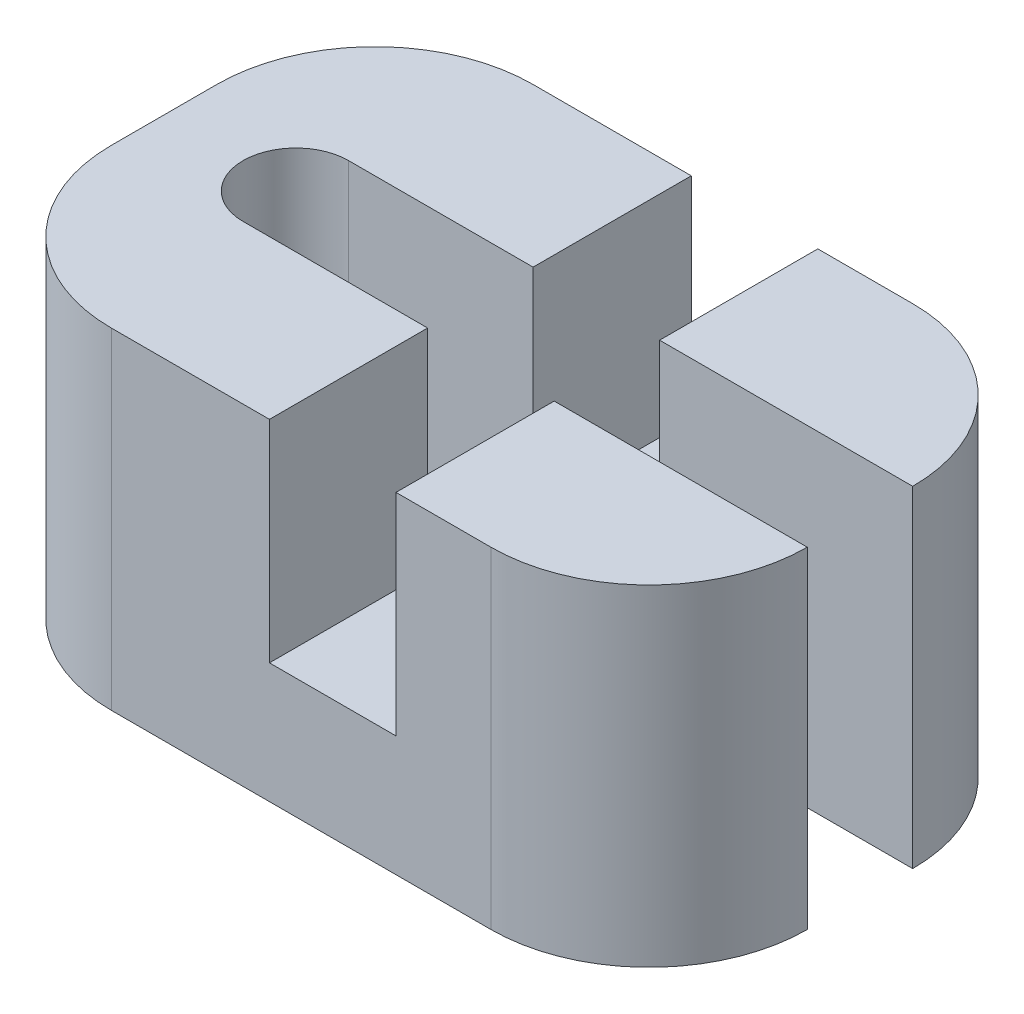
SolidWorks part; units mm, degrees
ref_plane "Alzado" through (0, 0, 0) normal (0, 0, 1) x (1, 0, 0)
ref_plane "Planta" through (0, 0, 0) normal (0, 1, 0) x (1, 0, 0)
ref_plane "Vista lateral" through (0, 0, 0) normal (1, 0, 0) x (0, 0, -1)
sketch "Croquis1" plane through (0, 0, 0) normal (0, 1, 0) x (1, 0, 0)
  line L0 (126.4716, 0) -> (0, 0) construction
  line L1 (15, 10) -> (-18, 10)
  line L2 (15, 10) -> (15, -10)
  line L3 (15, -10) -> (-18, -10)
  line L4 (-18, 10) -> (-18, -10)
  line L5 (0, 0) -> (0, 99.3902) construction
  dimension "D1" = 15
  dimension "D2" = 18
  dimension "D3" = 10
  dimension "D4" = 10
extrude "Saliente-Extruir1" add sketch "Croquis1" along normal blind 15.7
sketch "Croquis2" plane through (0, 15.7, 0) normal (0, 1, 0) x (1, 0, 0)
  line L0 (0, -13.5785) -> (0, 11.5662) construction
  line L1 (17.9678, 0) -> (-18.423, 0) construction
  circle A0 centre (-11.75, 0) radius 2.5
  circle A1 centre (11.75, 0) radius 2.5
  point P5 (-11.75, 0)
  point P6 (11.75, 0)
  dimension "D2" = 5
  dimension "D1" = 23.5
extrude "Cortar-Extruir1" cut sketch "Croquis2" against normal up to next contours A1 | A0
sketch "Croquis6" plane through (0, 15.7, 0) normal (0, 1, 0) x (1, 0, 0)
  line L0 (15, 10) -> (-18, 10) construction
  line L1 (-3, -10) -> (3, -10)
  line L2 (-3, -10) -> (-3, 10)
  line L3 (-3, 10) -> (3, 10)
  line L4 (3, -10) -> (3, 10)
  line L5 (-3, -10) -> (3, 10) construction
  line L6 (-3, 10) -> (3, -10) construction
  point P0 (0, 0)
  dimension "D1" = 6
extrude "Cortar-Extruir2" cut sketch "Croquis6" against normal blind 10
sketch "Croquis7" plane through (0, 15.7, 0) normal (0, 1, 0) x (1, 0, 0)
  line L0 (15, -10) -> (15, 10) construction
  line L1 (-11.75, 2.5) -> (15, 2.5)
  line L2 (-11.75, 2.5) -> (-11.75, -2.5)
  line L3 (-11.75, -2.5) -> (15, -2.5)
  line L4 (15, 2.5) -> (15, -2.5)
  circle A0 centre (-11.75, 0) radius 2.5 construction
extrude "Cortar-Extruir3" cut sketch "Croquis7" against normal up to next
fillet "Redondeo1" radius 7.5 4 edges at (-18, 7.85, -10) (-18, 7.85, 10) (15, 7.85, -10) (15, 7.85, 10)
sketch "Croquis8" plane through (-18, 0, 0) normal (-1, 0, 0) x (0, 0, 1)
  line L0 (-10, 15.7) -> (10, 14.6)
  line L3 (10, 15.7) -> (10, 0) construction
  dimension "D1" = 14.6
extrude "Cortar-Extruir4" [suppressed] cut sketch "Croquis8" against normal through all
sketch "Croquis9" plane through (0, 5.7, 0) normal (0, 1, 0) x (1, 0, 0)
  text T0 "L"
extrude "Cortar-Extruir5" [suppressed] cut sketch "Croquis9" against normal blind 0.5
